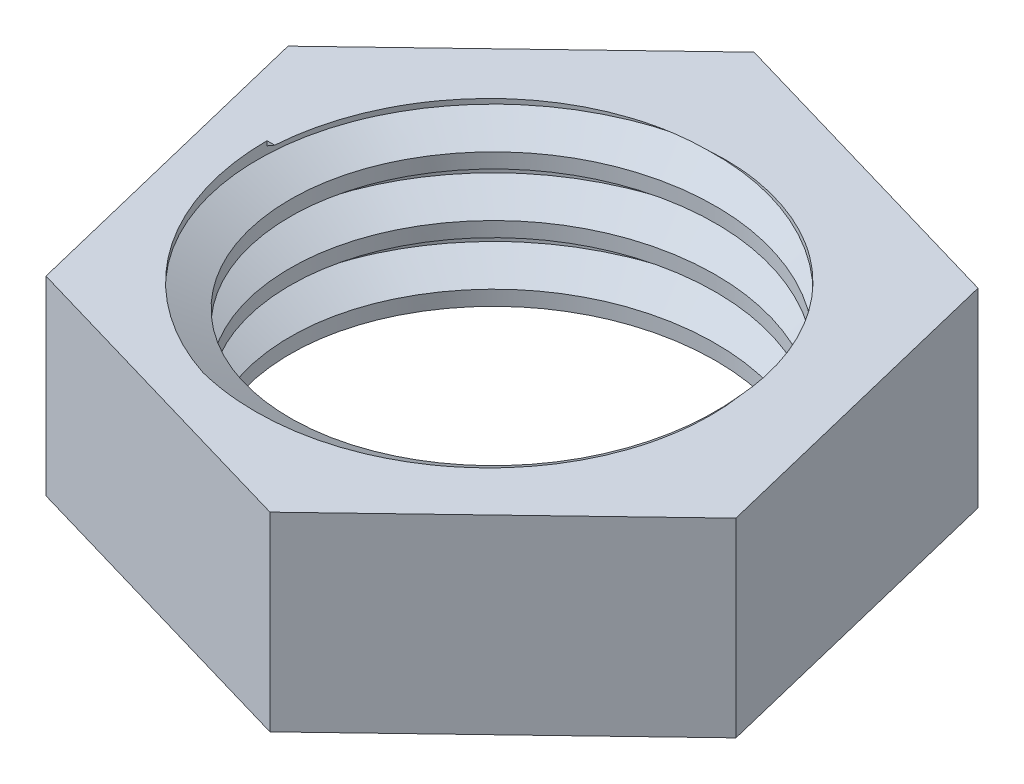
SolidWorks part; units mm, degrees
ref_plane "Front Plane" through (0, 0, 0) normal (0, 0, 1) x (1, 0, 0)
ref_plane "Top Plane" through (0, 0, 0) normal (0, 1, 0) x (1, 0, 0)
ref_plane "Right Plane" through (0, 0, 0) normal (1, 0, 0) x (0, 0, -1)
sketch "Sketch1" plane through (0, 0, 0) normal (0, 1, 0) x (1, 0, 0)
  line L1 (5.0076, 4.7879) -> (-1.6427, 6.7306)
  line L2 (-1.6427, 6.7306) -> (-6.6503, 1.9427)
  line L3 (-6.6503, 1.9427) -> (-5.0076, -4.7879)
  line L4 (-5.0076, -4.7879) -> (1.6427, -6.7306)
  line L5 (1.6427, -6.7306) -> (6.6503, -1.9427)
  line L6 (6.6503, -1.9427) -> (5.0076, 4.7879)
  circle A1 centre (0, 0) radius 6 construction
  dimension "D1" = 12
extrude "Boss-Extrude1" add sketch "Sketch1" along normal blind 4
sketch "Sketch2" plane through (0, 4, 0) normal (0, 1, 0) x (1, 0, 0)
  circle A0 centre (0, 0) radius 5.15
extrude "Cut-Extrude1" cut sketch "Sketch2" against normal through all
thread "Thread2" pitch 1.25 method extrude profile "Thread Profile2" start angle 0, offset 1, length 8, pitch 1.25, diameter 10.3
ref_plane "Plane2" through (-5.15, 5, 0) normal (0, 0, 1) x (-1, 0, 0)
sketch "Thread Profile2" plane through (-5.15, 5, 0) normal (0, 0, 1) x (-1, 0, 0)
  line L0 (0, 0) -> (0, 1.25) construction
  line L11 (0, 0) -> (0, 1.0937)
  line L12 (0, 1.0937) -> (-0.6766, 0.7031)
  line L13 (-0.6766, 0.7031) -> (-0.6766, 0.3906)
  line L15 (-0.6766, 0.3906) -> (0, 0)
  line L17 (-0.6766, 0.5469) -> (0, 0.5469) construction
  point P2 (0, 0)
  dimension "Pitch" = 1.25
  dimension "Profile_Angle" = 60
  dimension "Profile_Land" = 0.3125
  dimension "Profile_Height" = 0.6766
sketch "Sketch7" plane through (0, 0, 0) normal (0, -1, 0) x (1, 0, 0)
  circle A0 centre (-8.7275, 7.0288) radius 21.0283
extrude "Cut-Extrude2" cut sketch "Sketch7" along normal through all
sketch "Sketch8" plane through (0, 4, 0) normal (0, 1, 0) x (1, 0, 0)
  circle A0 centre (-10.1137, 5.9354) radius 21.0374
extrude "Cut-Extrude3" cut sketch "Sketch8" along normal through all
